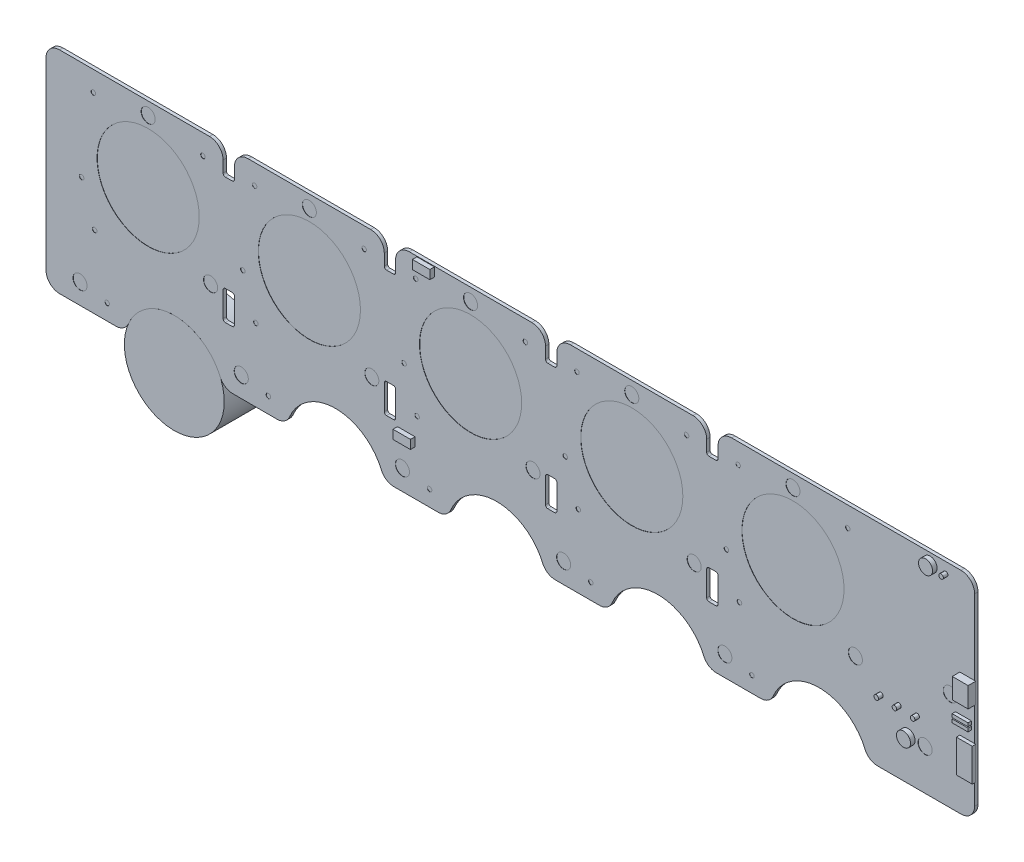
SolidWorks part; units mm, degrees
ref_plane "Plan de face" through (0, 0, 0) normal (0, 0, 1) x (1, 0, 0)
ref_plane "Plan de dessus" through (0, 0, 0) normal (0, 1, 0) x (1, 0, 0)
ref_plane "Plan de droite" through (0, 0, 0) normal (1, 0, 0) x (0, 0, -1)
sketch "Esquisse1" plane through (0, 0, 0) normal (0, 0, 1) x (1, 0, 0)
  line L0 (-142, 0) -> (-71, 0) construction
  line L1 (-187, 33) -> (222, 33)
  line L2 (-187, 33) -> (-187, -60)
  line L3 (-187, -60) -> (222, -60)
  line L4 (222, 33) -> (222, -60)
  line L5 (-71, 0) -> (0, 0) construction
  line L6 (0, 0) -> (71, 0) construction
  line L7 (71, 0) -> (142, 0) construction
  line L8 (-142, 0) -> (-187, 0) construction
  line L9 (142, 0) -> (222, 0) construction
  circle A0 centre (-142, 0) radius 22.5
  circle A1 centre (-71, 0) radius 22.5
  circle A2 centre (0, 0) radius 22.5
  circle A3 centre (71, 0) radius 22.5
  circle A4 centre (142, 0) radius 22.5
  dimension "D1" = 71
  dimension "D2" = 45
  dimension "D3" = 45
  dimension "D4" = 33
  dimension "D5" = 60
  dimension "D6" = 80
  dimension "D7" = 409
extrude "PCB_rectangulaire" add sketch "Esquisse1" against normal blind 1.5 contours L1 L4 L3 L2
extrude "position_trou" cut sketch "Esquisse1<3>" against normal blind 0.1 contours A0 | A1 | A2 | A3 | A4 region at (-142, 0, 0) region at (-71, 0, 0) region at (0, 0, 0) region at (71, 0, 0)
sketch "Esquisse1<3>" plane through (0, 0, 0) normal (0, 0, 1) x (1, 0, 0) same geometry as "Esquisse1"
sketch "Esquisse3" plane through (0, 0, 0) normal (0, 0, 1) x (1, 0, 0)
  line L0 (-187, 33) -> (222, 33) construction
  line L1 (-109, 33) -> (-104, 33)
  line L2 (-109, 33) -> (-109, 22)
  line L3 (-108, 21) -> (-105, 21)
  line L4 (-104, 33) -> (-104, 22)
  line L5 (-106.5, 21) -> (-106.5, 0) construction
  line L6 (-108, -21.5) -> (-105, -21.5)
  line L7 (-109, -22.5) -> (-109, -33.5)
  line L8 (-108, -34.5) -> (-105, -34.5)
  line L9 (-104, -22.5) -> (-104, -33.5)
  line L10 (-106.5, 0) -> (-106.5, -21.5) construction
  line L11 (-142, 0) -> (-71, 0) construction
  arc A0 (-105, 21) -> (-104, 22) centre (-105, 22) ccw
  arc A1 (-109, 22) -> (-108, 21) centre (-108, 22) ccw
  arc A2 (-105, -34.5) -> (-104, -33.5) centre (-105, -33.5) ccw
  arc A3 (-109, -33.5) -> (-108, -34.5) centre (-108, -33.5) ccw
  arc A4 (-105, -21.5) -> (-104, -22.5) centre (-105, -22.5) cw
  arc A5 (-108, -21.5) -> (-109, -22.5) centre (-108, -22.5) ccw
  point P17 (-104, -28)
  point P20 (-104, 21)
  point P25 (-104, -34.5)
  point P28 (-109, -34.5)
  point P31 (-104, -21.5)
  dimension "D5" = 1
  dimension "D1" = 5
  dimension "D2" = 12
  dimension "D3" = 13
  dimension "D4" = 28
extrude "passage_appui_flanc et passage jeton" cut sketch "Esquisse3" against normal through all
pattern_linear "Répétition linéaire1" count 4 spacing 71 along (1, 0, 0) of "passage_appui_flanc et passage jeton"
sketch "Esquisse2" plane through (0, 0, 0) normal (0, 0, 1) x (1, 0, 0)
  line L6 (-166.1376, 24.1376) -> (-164.5819, 22.5819) construction
  line L7 (-117.8624, 24.1376) -> (-119.4181, 22.5819) construction
  line L8 (-166.1376, 24.1376) -> (-117.8624, 24.1376) construction
  circle A0 centre (-171.2929, -10.7071) radius 1
  circle A1 centre (-165.5494, -28) radius 1
  circle A2 centre (-160.0562, -53.0562) radius 1
  circle A3 centre (-166.1376, 24.1376) radius 1
  circle A4 centre (-117.8624, 24.1376) radius 1
  circle A5 centre (-172, -51) radius 3.1
  circle A6 centre (-114.5, -23) radius 3.1
  circle A7 centre (-142, 27.5) radius 3.1
  circle A8 centre (211.2924, -16.5875) radius 3.1
  circle A9 centre (200.1924, -42.0875) radius 3.1
  dimension "D1" = 2
  dimension "D2" = 6.2
  dimension "D3" = 2.2
extrude "position_capteur-LED" cut sketch "Esquisse2" against normal blind 0.1
sketch "Esquisse4" plane through (0, 0, 0) normal (0, 0, 1) x (1, 0, 0)
  line L0 (-130.5, -65) -> (-59.5, -65) construction
  line L1 (-59.5, -65) -> (11.5, -65) construction
  line L2 (11.5, -65) -> (82.5, -65) construction
  line L3 (82.5, -65) -> (153.5, -65) construction
  line L4 (-142, 0) -> (-71, 0) construction
  circle A0 centre (-130.5, -65) radius 22
  circle A1 centre (-59.5, -65) radius 22 construction
  circle A2 centre (11.5, -65) radius 22 construction
  circle A3 centre (82.5, -65) radius 22 construction
  circle A4 centre (153.5, -65) radius 22 construction
  dimension "D1" = 44
  dimension "D2" = 11.5
  dimension "D3" = 65
extrude "echappement" cut sketch "Esquisse4" against normal through all
pattern_linear "Répétition linéaire3" count 5 spacing 71 along (1, 0, 0) of "position_capteur-LED", "echappement"
fillet "Congé1" radius 6 22 edges at (-187, -60, -0.75) (-187, 33, -0.75) (-109, 33, -0.75) (-104, 33, -0.75) (-38, 33, -0.75) (-33, 33, -0.75) (33, 33, -0.75) (38, 33, -0.75) (104, 33, -0.75) (109, 33, -0.75) (222, 33, -0.75) (222, -60, -0.75) (-109.0757, -60, -0.75) (-151.9243, -60, -0.75) (174.9243, -60, -0.75) (132.0757, -60, -0.75) (103.9243, -60, -0.75) (61.0757, -60, -0.75) (32.9243, -60, -0.75) (-9.9243, -60, -0.75) (-38.0757, -60, -0.75) (-80.9243, -60, -0.75)
sketch "Esquisse5" plane through (0, 0, 0) normal (0, 0, 1) x (1, 0, 0)
  line L0 (180.6924, -32.1875) -> (188.6924, -32.1875) construction
  line L1 (188.6924, -32.1875) -> (196.6924, -32.1875) construction
  line L3 (-23.6286, 32.7521) -> (-15.9214, 32.7521)
  line L4 (-23.6286, 32.7521) -> (-23.6286, 28.863)
  line L5 (-23.6286, 28.863) -> (-15.9214, 28.863)
  line L6 (-15.9214, 32.7521) -> (-15.9214, 28.863)
  line L7 (-32.1757, -36.2979) -> (-24.4686, -36.2979)
  line L8 (-32.1757, -36.2979) -> (-32.1757, -40.187)
  line L9 (-32.1757, -40.187) -> (-24.4686, -40.187)
  line L10 (-24.4686, -36.2979) -> (-24.4686, -40.187)
  line L11 (-28.3221, -36.5979) -> (-28.3221, -36.2979) construction
  line L13 (-24.7686, -38.2425) -> (-24.4686, -38.2425) construction
  line L15 (-19.775, 32.4521) -> (-19.775, 32.7521) construction
  line L17 (-16.2214, 30.8076) -> (-15.9214, 30.8076) construction
  circle A0 centre (180.6924, -32.1875) radius 1
  circle A1 centre (188.6924, -32.1875) radius 1
  circle A2 centre (196.6924, -32.1875) radius 1
  circle A3 centre (209.2395, 28.2642) radius 1
  circle A8 centre (192.6924, -42.0875) radius 3.1
  circle A9 centre (202.3924, 28.5125) radius 3.1
  dimension "D1" = 2
  dimension "D2" = 6.2
  dimension "D3" = 0.3
extrude "bouton et IR" add sketch "Esquisse5" along normal blind 2
sketch "Esquisse6" plane through (222, 0, 0) normal (1, 0, 0) x (0, 0, -1)
  line L1 (-3.335, -6.0675) -> (0, -6.0675)
  line L2 (-3.335, -6.0675) -> (-3.335, -15.0075)
  line L3 (-3.335, -15.0075) -> (0, -15.0075)
  line L4 (0, -6.0675) -> (0, -15.0075)
  line L5 (-1.535, -30.1124) -> (0, -30.1124)
  line L6 (-1.535, -30.1124) -> (-1.535, -44.5624)
  line L7 (-1.535, -44.5624) -> (0, -44.5624)
  line L8 (0, -30.1124) -> (0, -44.5624)
  line L9 (-3.4, -22.2375) -> (-1.9, -22.2375)
  line L10 (-3.4, -22.2375) -> (-3.4, -23.7375)
  line L11 (-3.4, -23.7375) -> (-1.9, -23.7375)
  line L12 (-1.9, -22.2375) -> (-1.9, -23.7375)
  line L19 (0, 27) -> (0, -54) construction
  line L20 (-1.9, -21.7375) -> (-1.9, -22.2375) construction
  line L21 (-3.4, -20.2375) -> (-1.9, -20.2375)
  line L22 (-3.4, -20.2375) -> (-3.4, -21.7375)
  line L23 (-3.4, -21.7375) -> (-1.9, -21.7375)
  line L24 (-1.9, -20.2375) -> (-1.9, -21.7375)
  point P12 (-3.4, -20.9875)
  point P22 (-3.4, -22.9875)
  dimension "D1" = 6.4
  dimension "D2" = 1.5
  dimension "D3" = 2
  dimension "D4" = 3.4
extrude "cote_droit" add sketch "Esquisse6" against normal blind 7 from offset 0.5
extrude "degagement_jeton" add sketch "Esquisse4<2>" against normal blind 20 separate body contours A0
sketch "Esquisse4<2>" plane through (0, 0, 0) normal (0, 0, 1) x (1, 0, 0) same geometry as "Esquisse4"
sketch "repère_batterie" plane through (222, 0, 0) normal (1, 0, 0) x (0, 0, -1)
  line L0 (1.5, 27) -> (1.5, -54) construction
  line L1 (1.5, -43.8875) -> (5, -43.8875)
  line L2 (1.5, -43.8875) -> (1.5, -49.8875)
  line L3 (1.5, -49.8875) -> (5, -49.8875)
  line L4 (5, -43.8875) -> (5, -49.8875)
  line L9 (5.5, -43.8875) -> (5.5, -49.8875)
  line L10 (6.9, -43.8875) -> (6.9, -49.8875) construction
  line L11 (5, -49.8875) -> (5.5, -49.8875) construction
  line L12 (5.5, -49.8875) -> (6.9, -49.8875) construction
  line L13 (5, -43.8875) -> (5.5, -43.8875) construction
  line L14 (5.5, -43.8875) -> (6.9, -43.8875) construction
  line L15 (5, -43.6375) -> (54.5, -43.6375) construction
  line L16 (5, -21.6375) -> (54.5, -21.6375)
  line L17 (5, -21.6375) -> (5, -54.6375)
  line L18 (5, -54.6375) -> (54.5, -54.6375)
  line L19 (54.5, -21.6375) -> (54.5, -54.6375)
  line L20 (5, -43.3875) -> (5, -43.8875) construction
  line L21 (1.5, -37.3875) -> (5, -37.3875)
  line L22 (1.5, -37.3875) -> (1.5, -43.3875)
  line L23 (1.5, -43.3875) -> (5, -43.3875)
  line L24 (5, -37.3875) -> (5, -43.3875)
  line L25 (6, -48.1375) -> (6, -43.6375) construction
  line L26 (1.5, -60) -> (0, -60) construction
  line L27 (6, -43.6375) -> (6, -39.1375) construction
  point P14 (5, -46.8875)
  point P21 (5, -43.6375)
  dimension "D1" = 33
  dimension "D2" = 49.5
  dimension "D3" = 11
  dimension "D4" = 3.5
  dimension "D5" = 5.4
  dimension "D6" = 6
  dimension "D7" = 3.25
  dimension "D8" = 13.1125
  dimension "D9" = 5.3625
  dimension "D10" = 0.5
  dimension "D11" = 9
  dimension "D12" = 1
